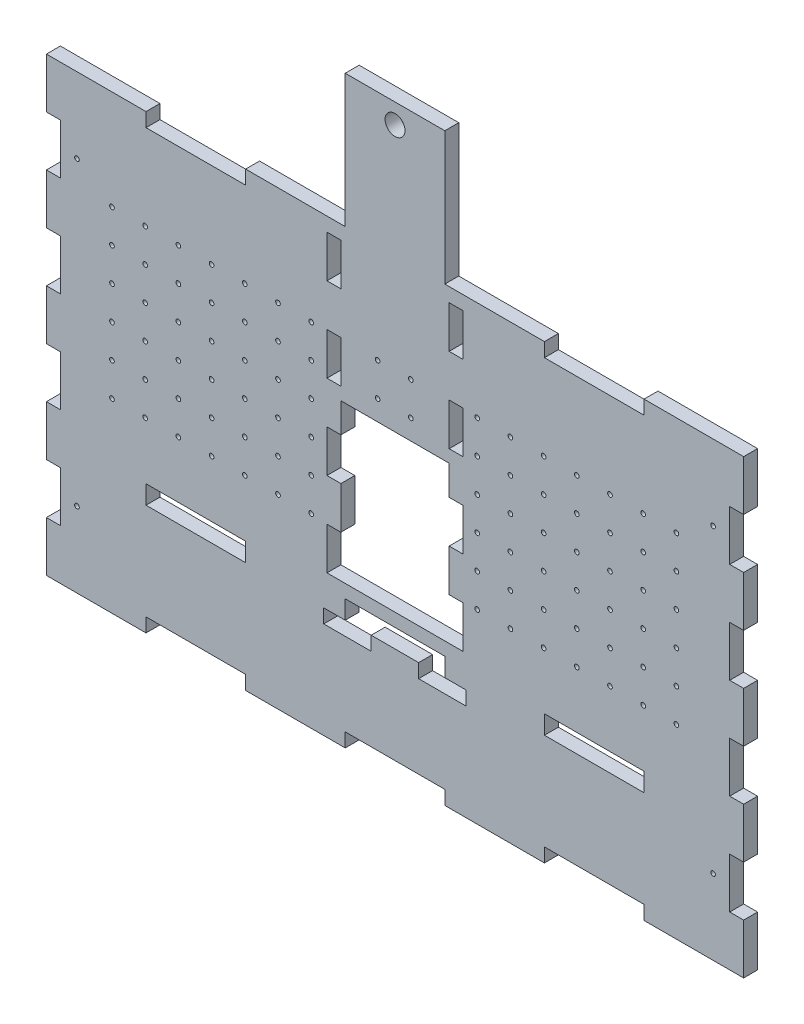
SolidWorks part; units mm, degrees
ref_plane "Front Plane" through (0, 0, 0) normal (0, 0, 1) x (1, 0, 0)
ref_plane "Top Plane" through (0, 0, 0) normal (0, 1, 0) x (1, 0, 0)
ref_plane "Right Plane" through (0, 0, 0) normal (1, 0, 0) x (0, 0, -1)
sketch "Sketch1" plane through (0, 0, 0) normal (0, 0, 1) x (1, 0, 0)
  line L1 (-127.8759, 88.4641) -> (138.8241, 88.4641)
  line L2 (-127.8759, 88.4641) -> (-127.8759, -84.2559)
  line L3 (-127.8759, -84.2559) -> (138.8241, -84.2559)
  line L4 (138.8241, 88.4641) -> (138.8241, -84.2559)
  dimension "D1" = 266.7
  dimension "D2" = 172.72
extrude "Boss-Extrude1" add sketch "Sketch1" along normal blind 5.334
sketch "Sketch2" plane through (0, 0, 5.334) normal (0, 0, 1) x (1, 0, 0)
  line L0 (-127.8759, -84.2559) -> (138.8241, -84.2559) construction
  line L1 (-89.7759, -84.2559) -> (-51.6759, -84.2559)
  line L2 (-89.7759, -84.2559) -> (-89.7759, -78.9219)
  line L3 (-89.7759, -78.9219) -> (-51.6759, -78.9219)
  line L4 (-51.6759, -84.2559) -> (-51.6759, -78.9219)
  line L5 (-89.7759, -78.9219) -> (-127.8759, -78.9219) construction
  line L6 (-13.5759, -84.2559) -> (24.5241, -84.2559)
  line L7 (-13.5759, -84.2559) -> (-13.5759, -78.9219)
  line L8 (-13.5759, -78.9219) -> (24.5241, -78.9219)
  line L9 (24.5241, -84.2559) -> (24.5241, -78.9219)
  line L10 (62.6241, -84.2559) -> (100.7241, -84.2559)
  line L11 (62.6241, -84.2559) -> (62.6241, -78.9219)
  line L12 (62.6241, -78.9219) -> (100.7241, -78.9219)
  line L13 (100.7241, -84.2559) -> (100.7241, -78.9219)
  line L14 (-127.8759, 88.4641) -> (-127.8759, -84.2559) construction
  line L15 (-51.6759, -78.9219) -> (-13.5759, -78.9219) construction
  line L16 (24.5241, -78.9219) -> (62.6241, -78.9219) construction
  line L17 (62.6241, -78.9219) -> (62.364, -79.7896) construction
  line L18 (100.7241, -78.9219) -> (138.8241, -78.9219) construction
  line L19 (138.8241, -84.2559) -> (138.8241, 88.4641) construction
  line L20 (-127.8759, 2.1041) -> (138.8241, 2.1041) construction
  line L21 (100.7241, 88.4641) -> (100.7241, 83.1301)
  line L22 (62.6241, 83.1301) -> (100.7241, 83.1301)
  line L23 (62.6241, 88.4641) -> (62.6241, 83.1301)
  line L24 (24.5241, 88.4641) -> (24.5241, 83.1301)
  line L25 (-13.5759, 83.1301) -> (24.5241, 83.1301)
  line L26 (-13.5759, 88.4641) -> (-13.5759, 83.1301)
  line L27 (-51.6759, 88.4641) -> (-51.6759, 83.1301)
  line L28 (-89.7759, 83.1301) -> (-51.6759, 83.1301)
  line L29 (-89.7759, 88.4641) -> (-89.7759, 83.1301)
  line L30 (62.6241, 88.4641) -> (100.7241, 88.4641)
  line L31 (-13.5759, 88.4641) -> (24.5241, 88.4641)
  line L32 (-89.7759, 88.4641) -> (-51.6759, 88.4641)
  dimension "D1" = 5.334
extrude "Cut-Extrude1" cut sketch "Sketch2" against normal through all
sketch "Sketch5" plane through (0, 0, 5.334) normal (0, 0, 1) x (1, 0, 0)
  line L0 (-51.6759, -34.8224) -> (-13.5759, -34.8224) construction
  line L1 (-89.7759, -34.8224) -> (-51.6759, -34.8224)
  line L2 (-89.7759, -34.8224) -> (-89.7759, -41.9344)
  line L3 (-89.7759, -41.9344) -> (-51.6759, -41.9344)
  line L4 (-51.6759, -34.8224) -> (-51.6759, -41.9344)
  line L5 (-13.5759, -34.8224) -> (24.5241, -34.8224)
  line L6 (-13.5759, -34.8224) -> (-13.5759, -41.9344)
  line L7 (-13.5759, -41.9344) -> (24.5241, -41.9344)
  line L8 (24.5241, -34.8224) -> (24.5241, -41.9344)
  line L9 (62.6241, -34.8224) -> (100.7241, -34.8224)
  line L10 (62.6241, -34.8224) -> (62.6241, -41.9344)
  line L11 (62.6241, -41.9344) -> (100.7241, -41.9344)
  line L12 (100.7241, -34.8224) -> (100.7241, -41.9344)
  line L13 (-51.6759, -41.9344) -> (-13.5759, -41.9344) construction
  line L14 (24.5241, -34.8224) -> (62.6241, -34.8224) construction
  line L15 (24.5241, -41.9344) -> (62.6241, -41.9344) construction
  line L16 (-89.7759, -34.8224) -> (-127.8759, -34.8224) construction
  line L17 (-127.8759, 88.4641) -> (-127.8759, -84.2559) construction
  line L18 (-89.7759, -41.9344) -> (-127.8759, -41.9344) construction
  line L19 (100.7241, -34.8224) -> (138.8241, -34.8224) construction
  line L20 (138.8241, -84.2559) -> (138.8241, 88.4641) construction
  line L21 (100.7241, -41.9344) -> (138.8241, -41.9344) construction
  dimension "D1" = 7.112
extrude "Cut-Extrude3" cut sketch "Sketch5" against normal through all
sketch "Sketch8" plane through (0, 0, 5.334) normal (0, 0, 1) x (1, 0, 0)
  line L0 (-13.5759, -41.9344) -> (24.5241, -41.9344) construction
  line L1 (-21.7977, -47.2684) -> (-3.6478, -47.2684)
  line L2 (-21.7977, -47.2684) -> (-21.7977, -41.9344)
  line L3 (-21.7977, -41.9344) -> (-3.6478, -41.9344)
  line L4 (-3.6478, -47.2684) -> (-3.6478, -41.9344)
  line L5 (-3.6478, -47.2684) -> (14.5022, -47.2684) construction
  line L6 (14.5022, -41.9344) -> (32.6521, -41.9344)
  line L7 (14.5022, -41.9344) -> (14.5022, -47.2684)
  line L8 (14.5022, -47.2684) -> (32.6521, -47.2684)
  line L9 (32.6521, -41.9344) -> (32.6521, -47.2684)
  line L10 (14.5022, -47.2684) -> (14.3218, -49.4005) construction
  line L11 (14.5022, -41.9344) -> (-3.6478, -41.9344) construction
  line L12 (62.6241, -34.8224) -> (62.6241, -41.9344) construction
  line L13 (-51.6759, -41.9344) -> (-51.6759, -34.8224) construction
  dimension "D1" = 5.334
  dimension "D2" = 29.972
  dimension "D3" = 29.8782
extrude "Cut-Extrude6" cut sketch "Sketch8" against normal through all
sketch "Sketch9" plane through (0, 0, 5.334) normal (0, 0, 1) x (1, 0, 0)
  line L0 (-127.8759, 88.4641) -> (-127.8759, -84.2559) construction
  line L1 (-127.8759, -65.0647) -> (-122.5419, -65.0647)
  line L2 (-127.8759, -65.0647) -> (-127.8759, -45.8736)
  line L3 (-127.8759, -45.8736) -> (-122.5419, -45.8736)
  line L4 (-122.5419, -65.0647) -> (-122.5419, -45.8736)
  line L5 (-122.5419, 69.273) -> (-122.5419, 88.4641) construction
  line L6 (-127.8759, -26.6825) -> (-122.5419, -26.6825)
  line L7 (-127.8759, -26.6825) -> (-127.8759, -7.4914)
  line L8 (-127.8759, -7.4914) -> (-122.5419, -7.4914)
  line L9 (-122.5419, -26.6825) -> (-122.5419, -7.4914)
  line L10 (-127.8759, 11.6997) -> (-122.5419, 11.6997)
  line L11 (-127.8759, 11.6997) -> (-127.8759, 30.8908)
  line L12 (-127.8759, 30.8908) -> (-122.5419, 30.8908)
  line L13 (-122.5419, 11.6997) -> (-122.5419, 30.8908)
  line L14 (-127.8759, 50.0819) -> (-122.5419, 50.0819)
  line L15 (-127.8759, 50.0819) -> (-127.8759, 69.273)
  line L16 (-127.8759, 69.273) -> (-122.5419, 69.273)
  line L17 (-122.5419, 50.0819) -> (-122.5419, 69.273)
  line L18 (-89.7759, 88.4641) -> (-127.8759, 88.4641) construction
  line L19 (-122.5419, 50.0819) -> (-122.5419, 30.8908) construction
  line L20 (-122.5419, 11.6997) -> (-122.5419, -7.4914) construction
  line L21 (-122.5419, -26.6825) -> (-122.5419, -45.8736) construction
  line L22 (-122.5419, -65.0647) -> (-122.5419, -84.2559) construction
  line L23 (-127.8759, -84.2559) -> (-89.7759, -84.2559) construction
  line L24 (5.4741, 83.1301) -> (5.4741, -78.9219) construction
  line L25 (-13.5759, 83.1301) -> (24.5241, 83.1301) construction
  line L26 (24.5241, -78.9219) -> (-13.5759, -78.9219) construction
  line L27 (133.4901, -65.0647) -> (133.4901, -84.2559) construction
  line L28 (133.4901, -26.6825) -> (133.4901, -45.8736) construction
  line L29 (133.4901, 11.6997) -> (133.4901, -7.4914) construction
  line L30 (133.4901, 50.0819) -> (133.4901, 30.8908) construction
  line L31 (133.4901, 69.273) -> (133.4901, 88.4641) construction
  line L32 (133.4901, 50.0819) -> (133.4901, 69.273)
  line L33 (138.8241, 69.273) -> (133.4901, 69.273)
  line L34 (138.8241, 50.0819) -> (138.8241, 69.273)
  line L35 (138.8241, 50.0819) -> (133.4901, 50.0819)
  line L36 (133.4901, 11.6997) -> (133.4901, 30.8908)
  line L37 (138.8241, 30.8908) -> (133.4901, 30.8908)
  line L38 (138.8241, 11.6997) -> (138.8241, 30.8908)
  line L39 (138.8241, 11.6997) -> (133.4901, 11.6997)
  line L40 (133.4901, -26.6825) -> (133.4901, -7.4914)
  line L41 (138.8241, -7.4914) -> (133.4901, -7.4914)
  line L42 (138.8241, -26.6825) -> (138.8241, -7.4914)
  line L43 (138.8241, -26.6825) -> (133.4901, -26.6825)
  line L44 (133.4901, -65.0647) -> (133.4901, -45.8736)
  line L45 (138.8241, -45.8736) -> (133.4901, -45.8736)
  line L46 (138.8241, -65.0647) -> (138.8241, -45.8736)
  line L47 (138.8241, -65.0647) -> (133.4901, -65.0647)
  dimension "D1" = 5.334
extrude "Cut-Extrude7" cut sketch "Sketch9" against normal through all
sketch "Sketch10" plane through (0, 88.4641, 0) normal (0, 1, 0) x (1, 0, 0)
  line L1 (24.5241, -5.334) -> (62.6241, -5.334)
  line L2 (24.5241, -5.334) -> (24.5241, 0)
  line L3 (24.5241, 0) -> (62.6241, 0)
  line L4 (62.6241, -5.334) -> (62.6241, 0)
extrude "Boss-Extrude2" add sketch "Sketch10" along normal blind 50.8
sketch "Sketch11" plane through (0, 0, 0) normal (0, 0, -1) x (-1, 0, 0)
  line L0 (-24.5241, 83.1301) -> (-24.5241, 139.2641) construction
  line L1 (-24.5241, 88.4641) -> (-31.1281, 88.4641)
  line L2 (-24.5241, 88.4641) -> (-24.5241, 129.1041)
  line L3 (-24.5241, 129.1041) -> (-31.1281, 129.1041)
  line L4 (-31.1281, 88.4641) -> (-31.1281, 129.1041)
  line L5 (13.5759, 88.4641) -> (51.6759, 88.4641) construction
  dimension "D1" = 6.604
  dimension "D2" = 40.64
  dimension "D3" = 0
extrude "Cut-Extrude8" cut sketch "Sketch11" against normal through all
sketch "Sketch12" plane through (0, 0, 5.334) normal (0, 0, 1) x (1, 0, 0)
  line L0 (62.6241, 139.2641) -> (62.6241, 83.1301) construction
  circle A0 centre (43.5741, 130.4765) radius 3.81
  dimension "D1" = 19.05
extrude "Cut-Extrude9" cut sketch "Sketch12" against normal through all
sketch "Sketch14" plane through (0, 0, 5.334) normal (0, 0, 1) x (1, 0, 0)
  line L0 (-89.7759, 88.4641) -> (-127.8759, 88.4641) construction
  circle A0 centre (-102.7976, 50.3641) radius 0.889
  circle A1 centre (-90.0976, 50.3641) radius 0.889
  circle A2 centre (-77.3976, 50.3641) radius 0.889
  circle A3 centre (-64.6976, 50.3641) radius 0.889
  circle A4 centre (-51.9976, 50.3641) radius 0.889
  circle A5 centre (-39.2976, 50.3641) radius 0.889
  circle A6 centre (-26.5976, 50.3641) radius 0.889
  circle A8 centre (-1.1976, 50.3641) radius 0.889
  circle A9 centre (11.5024, 50.3641) radius 0.889
  circle A11 centre (36.9024, 50.3641) radius 0.889
  circle A12 centre (49.6024, 50.3641) radius 0.889
  circle A13 centre (62.3024, 50.3641) radius 0.889
  circle A14 centre (75.0024, 50.3641) radius 0.889
  circle A15 centre (87.7024, 50.3641) radius 0.889
  circle A16 centre (100.4024, 50.3641) radius 0.889
  circle A17 centre (113.1024, 50.3641) radius 0.889
  circle A18 centre (-102.7976, 37.6641) radius 0.889
  circle A19 centre (-90.0976, 37.6641) radius 0.889
  circle A20 centre (-77.3976, 37.6641) radius 0.889
  circle A21 centre (-64.6976, 37.6641) radius 0.889
  circle A22 centre (-51.9976, 37.6641) radius 0.889
  circle A23 centre (-39.2976, 37.6641) radius 0.889
  circle A24 centre (-26.5976, 37.6641) radius 0.889
  circle A26 centre (-1.1976, 37.6641) radius 0.889
  circle A27 centre (11.5024, 37.6641) radius 0.889
  circle A29 centre (36.9024, 37.6641) radius 0.889
  circle A30 centre (49.6024, 37.6641) radius 0.889
  circle A31 centre (62.3024, 37.6641) radius 0.889
  circle A32 centre (75.0024, 37.6641) radius 0.889
  circle A33 centre (87.7024, 37.6641) radius 0.889
  circle A34 centre (100.4024, 37.6641) radius 0.889
  circle A35 centre (113.1024, 37.6641) radius 0.889
  circle A36 centre (-102.7976, 24.9641) radius 0.889
  circle A37 centre (-90.0976, 24.9641) radius 0.889
  circle A38 centre (-77.3976, 24.9641) radius 0.889
  circle A39 centre (-64.6976, 24.9641) radius 0.889
  circle A40 centre (-51.9976, 24.9641) radius 0.889
  circle A41 centre (-39.2976, 24.9641) radius 0.889
  circle A42 centre (-26.5976, 24.9641) radius 0.889
  circle A44 centre (-1.1976, 24.9641) radius 0.889
  circle A45 centre (11.5024, 24.9641) radius 0.889
  circle A47 centre (36.9024, 24.9641) radius 0.889
  circle A48 centre (49.6024, 24.9641) radius 0.889
  circle A49 centre (62.3024, 24.9641) radius 0.889
  circle A50 centre (75.0024, 24.9641) radius 0.889
  circle A51 centre (87.7024, 24.9641) radius 0.889
  circle A52 centre (100.4024, 24.9641) radius 0.889
  circle A53 centre (113.1024, 24.9641) radius 0.889
  circle A54 centre (-102.7976, 12.2641) radius 0.889
  circle A55 centre (-90.0976, 12.2641) radius 0.889
  circle A56 centre (-77.3976, 12.2641) radius 0.889
  circle A57 centre (-64.6976, 12.2641) radius 0.889
  circle A58 centre (-51.9976, 12.2641) radius 0.889
  circle A59 centre (-39.2976, 12.2641) radius 0.889
  circle A60 centre (-26.5976, 12.2641) radius 0.889
  circle A65 centre (36.9024, 12.2641) radius 0.889
  circle A66 centre (49.6024, 12.2641) radius 0.889
  circle A67 centre (62.3024, 12.2641) radius 0.889
  circle A68 centre (75.0024, 12.2641) radius 0.889
  circle A69 centre (87.7024, 12.2641) radius 0.889
  circle A70 centre (100.4024, 12.2641) radius 0.889
  circle A71 centre (113.1024, 12.2641) radius 0.889
  circle A72 centre (-102.7976, -0.4359) radius 0.889
  circle A73 centre (-90.0976, -0.4359) radius 0.889
  circle A74 centre (-77.3976, -0.4359) radius 0.889
  circle A75 centre (-64.6976, -0.4359) radius 0.889
  circle A76 centre (-51.9976, -0.4359) radius 0.889
  circle A77 centre (-39.2976, -0.4359) radius 0.889
  circle A78 centre (-26.5976, -0.4359) radius 0.889
  circle A79 centre (-13.8976, -0.4359) radius 0.889
  circle A80 centre (-1.1976, -0.4359) radius 0.889
  circle A81 centre (11.5024, -0.4359) radius 0.889
  circle A82 centre (24.2024, -0.4359) radius 0.889
  circle A83 centre (36.9024, -0.4359) radius 0.889
  circle A84 centre (49.6024, -0.4359) radius 0.889
  circle A85 centre (62.3024, -0.4359) radius 0.889
  circle A86 centre (75.0024, -0.4359) radius 0.889
  circle A87 centre (87.7024, -0.4359) radius 0.889
  circle A88 centre (100.4024, -0.4359) radius 0.889
  circle A89 centre (113.1024, -0.4359) radius 0.889
  circle A90 centre (-102.7976, -13.1359) radius 0.889
  circle A91 centre (-90.0976, -13.1359) radius 0.889
  circle A92 centre (-77.3976, -13.1359) radius 0.889
  circle A93 centre (-64.6976, -13.1359) radius 0.889
  circle A94 centre (-51.9976, -13.1359) radius 0.889
  circle A95 centre (-39.2976, -13.1359) radius 0.889
  circle A96 centre (-26.5976, -13.1359) radius 0.889
  circle A97 centre (-13.8976, -13.1359) radius 0.889
  circle A98 centre (-1.1976, -13.1359) radius 0.889
  circle A99 centre (11.5024, -13.1359) radius 0.889
  circle A100 centre (24.2024, -13.1359) radius 0.889
  circle A101 centre (36.9024, -13.1359) radius 0.889
  circle A102 centre (49.6024, -13.1359) radius 0.889
  circle A103 centre (62.3024, -13.1359) radius 0.889
  circle A104 centre (75.0024, -13.1359) radius 0.889
  circle A105 centre (87.7024, -13.1359) radius 0.889
  circle A106 centre (100.4024, -13.1359) radius 0.889
  circle A107 centre (113.1024, -13.1359) radius 0.889
  circle A108 centre (-1.1976, 12.2641) radius 0.889 [skipped]
  circle A110 centre (11.5024, 12.2641) radius 0.889 [skipped]
  circle A116 centre (24.2024, 50.3641) radius 0.889 [skipped]
  circle A117 centre (-13.8976, 50.3641) radius 0.889 [skipped]
  dimension "D1" = 18
  dimension "D2" = 38.1
  dimension "D4" = 1.778
  dimension "D3" = 6
extrude "Cut-Extrude11" cut sketch "Sketch14" against normal through all
sketch "Sketch15" plane through (0, 0, 5.334) normal (0, 0, 1) x (1, 0, 0)
  line L1 (31.1281, 129.1041) -> (24.5241, 129.1041)
  line L2 (31.1281, 129.1041) -> (31.1281, 139.2641)
  line L3 (31.1281, 139.2641) -> (24.5241, 139.2641)
  line L4 (24.5241, 129.1041) -> (24.5241, 139.2641)
extrude "Cut-Extrude12" cut sketch "Sketch15" against normal through all
sketch "Sketch16" plane through (0, 0, 5.334) normal (0, 0, 1) x (1, 0, 0)
  line L0 (5.4741, 83.1301) -> (5.4741, -78.9219) construction
  line L1 (-15.2269, 29.9476) -> (26.1751, 29.9476)
  line L2 (-15.2269, 29.9476) -> (-15.2269, -29.7424)
  line L3 (-15.2269, -29.7424) -> (26.1751, -29.7424)
  line L4 (26.1751, 29.9476) -> (26.1751, -29.7424)
  line L5 (-13.5759, 83.1301) -> (24.5241, 83.1301) construction
  line L6 (24.5241, -78.9219) -> (-13.5759, -78.9219) construction
  line L7 (24.5241, -34.8224) -> (-13.5759, -34.8224) construction
  dimension "D1" = 59.69
  dimension "D2" = 41.402
  dimension "D3" = 20.701
  dimension "D4" = 5.08
extrude "Cut-Extrude13" cut sketch "Sketch16" against normal through all
sketch "Sketch17" plane through (0, 0, 5.334) normal (0, 0, 1) x (1, 0, 0)
  line L0 (-15.2269, 29.9476) -> (-15.2269, -29.7424) construction
  line L1 (-15.2269, -29.7424) -> (-20.5609, -29.7424)
  line L2 (-15.2269, -29.7424) -> (-15.2269, -13.6178)
  line L3 (-15.2269, -13.6178) -> (-20.5609, -13.6178)
  line L4 (-20.5609, -29.7424) -> (-20.5609, -13.6178)
  line L5 (-15.2269, 2.5069) -> (-20.5609, 2.5069)
  line L6 (-15.2269, 2.5069) -> (-15.2269, 18.6315)
  line L7 (-15.2269, 18.6315) -> (-20.5609, 18.6315)
  line L8 (-20.5609, 2.5069) -> (-20.5609, 18.6315)
  line L9 (-20.5609, -13.6178) -> (-20.5609, 2.5069) construction
  line L10 (-20.5609, 50.8808) -> (-15.2269, 50.8808)
  line L11 (-20.5609, 50.8808) -> (-20.5609, 34.7562)
  line L12 (-20.5609, 34.7562) -> (-15.2269, 34.7562)
  line L13 (-15.2269, 50.8808) -> (-15.2269, 34.7562)
  line L14 (-20.5609, 67.0055) -> (-15.2269, 67.0055)
  line L15 (-20.5609, 67.0055) -> (-20.5609, 83.1301)
  line L16 (-20.5609, 83.1301) -> (-15.2269, 83.1301)
  line L17 (-15.2269, 67.0055) -> (-15.2269, 83.1301)
  line L18 (-20.5609, 18.6315) -> (-20.5609, 34.7562) construction
  line L19 (-20.5609, 67.0055) -> (-20.5609, 50.8808) construction
  line L20 (5.4741, 83.1301) -> (5.4741, -78.9219) construction
  line L21 (-13.5759, 83.1301) -> (24.5241, 83.1301) construction
  line L22 (24.5241, -78.9219) -> (-13.5759, -78.9219) construction
  line L23 (31.5091, 67.0055) -> (31.5091, 50.8808) construction
  line L24 (31.5091, 18.6315) -> (31.5091, 34.7562) construction
  line L25 (31.5091, -13.6178) -> (31.5091, 2.5069) construction
  line L26 (26.1751, 67.0055) -> (26.1751, 83.1301)
  line L27 (31.5091, 83.1301) -> (26.1751, 83.1301)
  line L28 (31.5091, 67.0055) -> (31.5091, 83.1301)
  line L29 (31.5091, 67.0055) -> (26.1751, 67.0055)
  line L30 (26.1751, 50.8808) -> (26.1751, 34.7562)
  line L31 (31.5091, 34.7562) -> (26.1751, 34.7562)
  line L32 (31.5091, 50.8808) -> (31.5091, 34.7562)
  line L33 (31.5091, 50.8808) -> (26.1751, 50.8808)
  line L34 (31.5091, 2.5069) -> (31.5091, 18.6315)
  line L35 (26.1751, 18.6315) -> (31.5091, 18.6315)
  line L36 (26.1751, 2.5069) -> (26.1751, 18.6315)
  line L37 (26.1751, 2.5069) -> (31.5091, 2.5069)
  line L38 (31.5091, -29.7424) -> (31.5091, -13.6178)
  line L39 (26.1751, -13.6178) -> (31.5091, -13.6178)
  line L40 (26.1751, -29.7424) -> (26.1751, -13.6178)
  line L41 (26.1751, -29.7424) -> (31.5091, -29.7424)
  dimension "D1" = 0
  dimension "D2" = 5.334
  dimension "D3" = 5.334
  dimension "D4" = 5.334
extrude "Cut-Extrude14" cut sketch "Sketch17" against normal through all
sketch "Sketch18" plane through (0, 0, 5.334) normal (0, 0, 1) x (1, 0, 0)
  line L0 (24.5241, 83.1301) -> (24.5241, 148.9274) construction
  line L1 (31.1281, 139.2641) -> (62.6241, 139.2641) construction
  line L2 (-13.5759, 83.1301) -> (24.5241, 83.1301)
  line L3 (-13.5759, 83.1301) -> (-13.5759, 139.2641)
  line L4 (-13.5759, 139.2641) -> (24.5241, 139.2641)
  line L5 (24.5241, 83.1301) -> (24.5241, 139.2641)
  dimension "D1" = 0
extrude "Boss-Extrude3" add sketch "Sketch18" against normal blind 5.334
sketch "Sketch19" plane through (0, 0, 5.334) normal (0, 0, 1) x (1, 0, 0)
  line L1 (31.1281, 88.4641) -> (65.8849, 88.4641)
  line L2 (31.1281, 88.4641) -> (31.1281, 143.4078)
  line L3 (31.1281, 143.4078) -> (65.8849, 143.4078)
  line L4 (65.8849, 88.4641) -> (65.8849, 143.4078)
extrude "Cut-Extrude15" cut sketch "Sketch19" against normal through all
sketch "Sketch20" plane through (0, 0, 5.334) normal (0, 0, 1) x (1, 0, 0)
  line L0 (5.4741, 139.2641) -> (5.4741, 29.9476) construction
  line L1 (24.5241, 139.2641) -> (-13.5759, 139.2641) construction
  circle A0 centre (5.4741, 131.6441) radius 3.81
  point P8 (-119.488, 123.581)
  dimension "D1" = 7.62
  dimension "D3" = 7.62
  dimension "D2" = 0
extrude "Cut-Extrude16" cut sketch "Sketch20" against normal through all contours A0
sketch "Sketch21" plane through (0, 0, 5.334) normal (0, 0, 1) x (1, 0, 0)
  line L0 (133.4901, 59.6775) -> (-122.5419, 59.6775) construction
  line L1 (133.4901, 69.273) -> (133.4901, 50.0819) construction
  line L2 (-122.5419, 50.0819) -> (-122.5419, 69.273) construction
  line L3 (-122.5419, -55.4692) -> (133.4901, -55.4692) construction
  line L4 (-122.5419, -65.0647) -> (-122.5419, -45.8736) construction
  line L5 (133.4901, -45.8736) -> (133.4901, -65.0647) construction
  line L6 (138.8241, 2.1041) -> (-127.8759, 2.1041) construction
  line L7 (138.8241, -7.4914) -> (138.8241, 11.6997) construction
  line L8 (-127.8759, 11.6997) -> (-127.8759, -7.4914) construction
  line L9 (5.4741, 139.2641) -> (5.4741, -78.9219) construction
  line L10 (24.5241, 139.2641) -> (-13.5759, 139.2641) construction
  line L11 (24.5241, -78.9219) -> (-13.5759, -78.9219) construction
  circle A0 centre (127.1401, 59.6775) radius 0.889
  circle A1 centre (-116.1919, 59.6775) radius 0.889
  circle A2 centre (-116.1919, -55.4692) radius 0.889
  circle A3 centre (127.1401, -55.4692) radius 0.889
  dimension "D1" = 1.778
  dimension "D2" = 0
  dimension "D3" = 6.35
extrude "Cut-Extrude17" cut sketch "Sketch21" against normal through all
equation "\"MDF\"= .21in"
equation "\"Foamcore\"= .13in"
equation "\"Gmaterial\"= \"MDF\""
equation "\"D1@Boss-Extrude1\"=\"MDF\""
equation "\"D1@Sketch2\"=\"MDF\""
equation "\"D1@Sketch5\"=\"MDF\"+0.07"
equation "\"D1@Sketch8\"=\"MDF\""
equation "\"D1@Sketch9\"=\"MDF\""
equation "\"D1@Sketch11\"=\"MDF\"+.05"
equation "\"D2@Sketch17\"=\"MDF\""
equation "\"D3@Sketch17\"=\"MDF\""
equation "\"D4@Sketch17\"=\"MDF\""
equation "\"D1@Boss-Extrude3\"=\"MDF\""
